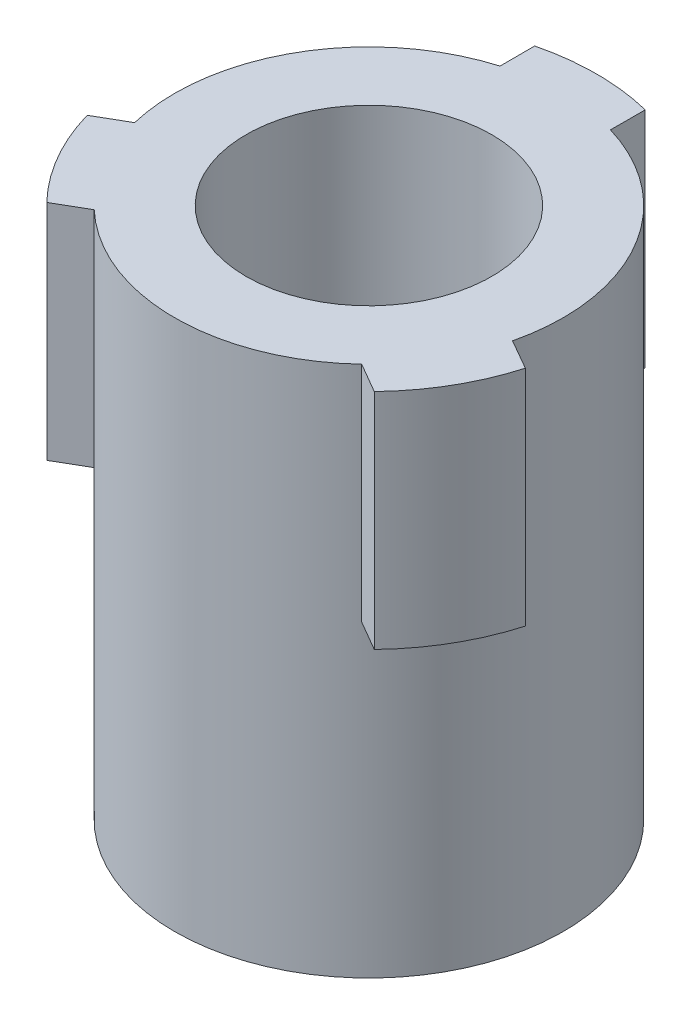
SolidWorks part; units mm, degrees
ref_plane "Front Plane" through (0, 0, 0) normal (0, 0, 1) x (1, 0, 0)
ref_plane "Top Plane" through (0, 0, 0) normal (0, 1, 0) x (1, 0, 0)
ref_plane "Right Plane" through (0, 0, 0) normal (1, 0, 0) x (0, 0, -1)
sketch "Sketch1" plane through (0, 0, 0) normal (0, 1, 0) x (1, 0, 0)
  circle A0 centre (0, 0) radius 8.7
  circle A1 centre (0, 0) radius 5.5
  dimension "D1" = 17.4
  dimension "D3" = 11
extrude "Boss-Extrude1" add sketch "Sketch1" along normal blind 68.8
sketch "Sketch2" plane through (0, 0, 0) normal (0, -1, 0) x (1, 0, 0)
  circle A0 centre (0, 0) radius 5.5
  circle A1 centre (0, 0) radius 16
  dimension "D1" = 32
extrude "Boss-Extrude2" add sketch "Sketch2" along normal blind 4
fillet "Fillet1" radius 2 2 edges at (0, -4, -16) (0, 0, -16)
fillet "Fillet2" radius 1 1 edges at (0, 0, -8.7)
sketch "Sketch7" plane through (0, 68.8, 0) normal (0, 1, 0) x (1, 0, 0)
  line L0 (0, 0) -> (0, 11.5063) construction
  line L1 (0, 0) -> (9.9648, -5.7532) construction
  line L2 (0, 0) -> (-8.8335, -5.1) construction
  line L9 (-8.4598, -2.0303) -> (-9.806, -2.8076)
  line L11 (-5.9882, -6.3112) -> (-7.3314, -7.0915)
  line L12 (-2.4716, 8.3415) -> (-2.4757, 9.895)
  line L19 (2.4716, 8.3415) -> (2.4757, 9.895)
  line L20 (8.4598, -2.0303) -> (9.8072, -2.8035)
  line L21 (5.9882, -6.3112) -> (7.3314, -7.0915)
  arc A0 (-8.4598, -2.0303) -> (-5.9882, -6.3112) centre (0, 0) ccw
  arc A1 (-9.806, -2.8076) -> (-7.3314, -7.0915) centre (0, 0) ccw
  arc A2 (2.4716, 8.3415) -> (-2.4716, 8.3415) centre (0, 0) ccw
  arc A3 (2.4757, 9.895) -> (-2.4757, 9.895) centre (0, 0) ccw
  arc A4 (5.9882, -6.3112) -> (8.4598, -2.0303) centre (0, 0) ccw
  arc A5 (7.3314, -7.0915) -> (9.8072, -2.8035) centre (0, 0) ccw
  point P5 (2.5, 0)
  point P6 (2.5, 11.5063)
  point P8 (-9.9648, -5.7532)
  point P10 (-1.25, 2.1651)
  point P11 (-11.2148, -3.5881)
  point P12 (-1.25, -2.1651)
  point P13 (8.7148, -7.9182)
  point P14 (-2.5, 0)
  point P15 (-2.5, 11.5063)
  point P16 (1.25, -2.1651)
  point P17 (-8.7148, -7.9182)
  point P18 (1.25, 2.1651)
  point P19 (11.2148, -3.5881)
  dimension "D2" = 17.4
  dimension "D3" = 1.5
  dimension "D1" = 3
extrude "Boss-Extrude6" add sketch "Sketch7" against normal blind 10
ref_plane "Plane1" through (0, 45, 0) normal (0, 1, 0) x (1, 0, 0)
sketch "Sketch10" plane through (0, 45, 0) normal (0, 1, 0) x (1, 0, 0)
  circle A0 centre (0, 0) radius 8.7
  circle A1 centre (0, 0) radius 7.2
  dimension "D2" = 17.4
extrude "Cut-Extrude1" cut sketch "Sketch10" against normal blind 23
sketch "Sketch11" plane through (0, 45, 0) normal (0, -1, 0) x (1, 0, 0)
  circle A0 centre (0, 0) radius 18.5461
extrude "Cut-Extrude2" cut sketch "Sketch11" along normal through all
sketch "Sketch12" plane through (0, 45, 0) normal (0, -1, 0) x (1, 0, 0)
  circle A0 centre (0, 0) radius 7.3
  dimension "D1" = 14.6
extrude "Cut-Extrude3" cut sketch "Sketch12" against normal blind 15
equation "\"clearance\"= 0.3mm ' Freely and easily sliding. Used as a gap between the telescopic sections."
equation "\"clearance2\" = 0.1mm ' Used as a gap between rings next to each other."
equation "\"interference\"= 0.1mm ' This is like clearance1 but when two parts should just fit together rather than freely spin."
equation "\"D1@Sketch1\"=18.00mm-\"clearance\"*2"
equation "\"pegLength\"= 1.5mm ' The length of the pegs that stick out from the telescopic sections."
equation "\"D2@Sketch7\"=18.00mm-\"clearance\"*2"
equation "\"D3@Sketch7\"=\"pegLength\""
equation "\"D2@Sketch10\"=18.00mm-\"clearance\"*2"
equation "\"D1@Sketch12\"=18.00mm-\"clearance\"*2-3 +\"interference\"*2"
